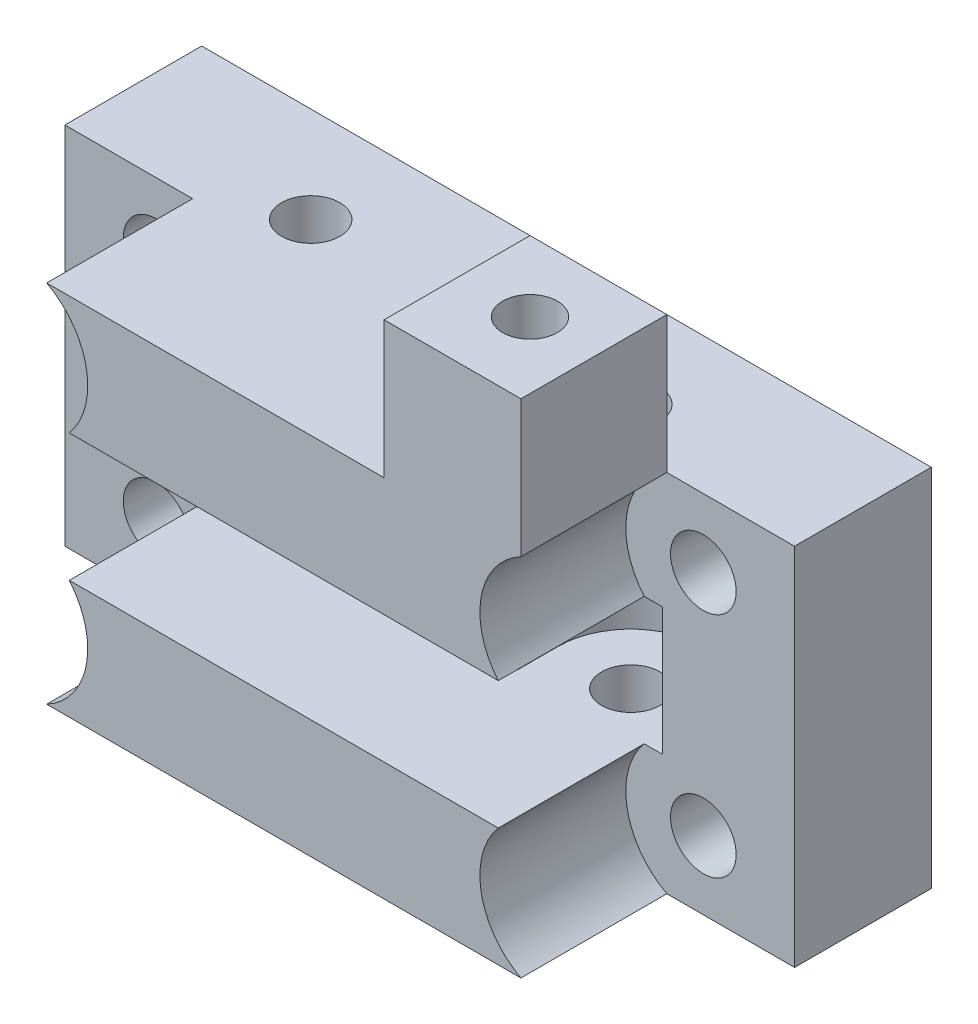
SolidWorks part; units mm, degrees
ref_plane "Front Plane" through (0, 0, 0) normal (0, 0, 1) x (1, 0, 0)
ref_plane "Top Plane" through (0, 0, 0) normal (0, 1, 0) x (1, 0, 0)
ref_plane "Right Plane" through (0, 0, 0) normal (1, 0, 0) x (0, 0, -1)
sketch "Sketch1" plane through (0, 0, 0) normal (0, 0, 1) x (1, 0, 0)
  line L0 (-25.4, 12.7) -> (25.4, -12.7) construction
  line L1 (-25.4, -12.7) -> (25.4, -12.7)
  line L2 (-25.4, -12.7) -> (-25.4, 12.7)
  line L3 (-25.4, 12.7) -> (25.4, 12.7)
  line L4 (25.4, -12.7) -> (25.4, 12.7)
  point P6 (0, 0)
  dimension "D1" = 50.8
  dimension "D2" = 25.4
extrude "Boss-Extrude1" add sketch "Sketch1" along normal mid plane 9.525
sketch "Sketch2" plane through (0, 0, 4.7625) normal (0, 0, 1) x (1, 0, 0)
  line L0 (-25.4, -12.7) -> (25.4, -12.7) construction
  line L1 (-25.4, 12.7) -> (-25.4, -12.7) construction
  circle A0 centre (-19.05, 7.9375) radius 2.286
  dimension "D1" = 4.572
  dimension "D2" = 20.6375
  dimension "D3" = 6.35
extrude "Cut-Extrude1" cut sketch "Sketch2" against normal through all
sketch "Sketch4" plane through (0, 0, 0) normal (0, 1, 0) x (1, 0, 0)
  line L7 (25.4, -4.7625) -> (-25.4, -4.7625) construction
  line L8 (-16.2242, -1.905) -> (-16.2243, -4.7625)
  line L9 (-6.0642, -1.905) -> (-6.0643, -4.7625)
  line L10 (-6.0643, -4.7625) -> (-16.2243, -4.7625)
  line L11 (-25.4, -4.7625) -> (-25.4, 4.7625) construction
  arc A2 (-6.0642, -1.905) -> (-16.2242, -1.905) centre (-11.1442, -1.905) ccw
  dimension "D1" = 10.16
  dimension "D2" = 2.8575
  dimension "D3" = 14.2558
extrude "Cut-Extrude2" cut sketch "Sketch4" against normal mid plane 8.89
sketch "Sketch5" plane through (0, 12.7, 0) normal (0, 1, 0) x (1, 0, 0)
  line L0 (25.4, -4.7625) -> (-25.4, -4.7625) construction
  line L1 (-25.4, -4.7625) -> (-25.4, 4.7625) construction
  circle A0 centre (-11.1442, -1.905) radius 2.032
  dimension "D3" = 4.064
  dimension "D1" = 2.8575
  dimension "D2" = 14.2558
extrude "Cut-Extrude3" cut sketch "Sketch5" against normal through all
sketch "Sketch6" plane through (0, 0, 4.7625) normal (0, 0, 1) x (1, 0, 0)
  line L0 (-16.51, 12.7) -> (16.51, 12.7)
  line L1 (25.4, 12.7) -> (-25.4, 12.7) construction
  line L2 (-14.9347, 4.445) -> (14.9347, 4.445)
  line L3 (-16.2242, 4.445) -> (-6.0642, 4.445) construction
  arc A0 (-14.9347, 4.445) -> (-16.51, 12.7) centre (-19.05, 7.9375) ccw
  arc A1 (16.51, 12.7) -> (14.9347, 4.445) centre (19.05, 7.9375) ccw
  dimension "D1" = 10.795
  dimension "D2" = 38.1
  dimension "D3" = 29.8695
extrude "Boss-Extrude2" add sketch "Sketch6" along normal blind 10.16
mirror "Mirror1" about plane through (0, 0, 0) normal (0, 1, 0) of "Boss-Extrude2", "Cut-Extrude1"
mirror "Mirror2" about plane through (0, 0, 0) normal (1, 0, 0) of "Cut-Extrude3", "Mirror1", "Cut-Extrude2"
sketch "Sketch7" plane through (0, 12.7, 0) normal (0, 1, 0) x (1, 0, 0)
  line L0 (16.51, -14.9225) -> (-16.51, -14.9225) construction
  line L1 (16.51, -4.7625) -> (6.985, -4.7625)
  line L2 (16.51, -4.7625) -> (16.51, -14.9225)
  line L3 (16.51, -14.9225) -> (6.985, -14.9225)
  line L4 (6.985, -4.7625) -> (6.985, -14.9225)
  dimension "D1" = 9.525
extrude "Boss-Extrude3" add sketch "Sketch7" along normal blind 9.525
sketch "Sketch8" plane through (0, 22.225, 0) normal (0, 1, 0) x (1, 0, 0)
  line L0 (11.8867, -9.6673) -> (6.985, -9.8425) construction
  line L1 (6.985, -4.7625) -> (6.985, -14.9225) construction
  line L2 (11.8867, -9.6673) -> (11.8867, -4.7625) construction
  line L3 (16.51, -4.7625) -> (6.985, -4.7625) construction
  circle A0 centre (11.8867, -9.6673) radius 1.905
  dimension "D1" = 3.81
extrude "Cut-Extrude4" cut sketch "Sketch8" against normal blind 6.35 contours A0
